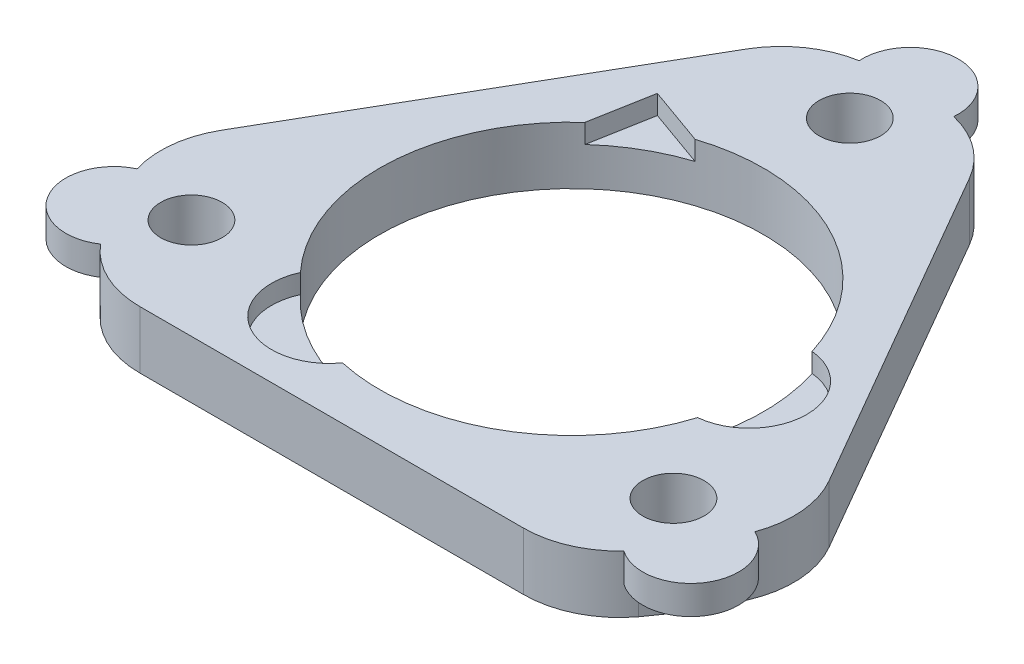
SolidWorks part; units mm, degrees
ref_plane "Спереди" through (0, 0, 0) normal (0, 0, 1) x (1, 0, 0)
ref_plane "Сверху" through (0, 0, 0) normal (0, 1, 0) x (1, 0, 0)
ref_plane "Справа" through (0, 0, 0) normal (1, 0, 0) x (0, 0, -1)
sketch "Sketch1" plane through (0, 0, 0) normal (0, 1, 0) x (1, 0, 0)
  circle A0 centre (0, 0) radius 18.5
  dimension "D1" = 37
extrude "Boss-Extrude1" add sketch "Sketch1" along normal blind 3.5
sketch "Sketch2" plane through (0, 0, 0) normal (0, 1, 0) x (1, 0, 0)
  circle A0 centre (0, 0) radius 35
  circle A1 centre (0, 0) radius 20
  circle A2 centre (0, 0) radius 29 construction
  circle A3 centre (0, 29) radius 2.8
  circle A4 centre (25.1147, -14.5) radius 2.8
  circle A5 centre (-25.1147, -14.5) radius 2.8
  point P16 (0, 0)
  dimension "D2" = 58
  dimension "D3" = 40
  dimension "D4" = 70
  dimension "D1" = 3
extrude "Boss-Extrude2" add sketch "Sketch2" along normal blind 6
sketch "Sketch4" plane through (0, 0, 0) normal (0, -1, 0) x (1, 0, 0)
  circle A0 centre (-25.1147, 14.5) radius 3.2
  circle A1 centre (25.1147, 14.5) radius 3.2
  circle A2 centre (0, -29) radius 3.2
  point P9 (0, 0)
  dimension "D1" = 3
sketch "Sketch5" plane through (0, 6, 0) normal (0, 1, 0) x (1, 0, 0)
  circle A0 centre (-30.4536, -17.2504) radius 5
  circle A1 centre (0, 0) radius 35 construction
  circle A2 centre (0.2875, 34.9988) radius 5
  circle A3 centre (30.1661, -17.7484) radius 5
  point P10 (0, 0)
  dimension "D1" = 3
extrude "Boss-Extrude4" add sketch "Sketch5" against normal blind 3
sketch "Sketch3" plane through (0, 3.5, 0) normal (0, 1, 0) x (1, 0, 0)
  circle A0 centre (0, 0) radius 18.5
  dimension "D1" = 37
extrude "Cut-Extrude1" cut sketch "Sketch3" against normal blind 10
sketch "Sketch12" plane through (0, 6, 0) normal (0, 1, 0) x (1, 0, 0)
  line L1 (0, 50) -> (-43.3013, -25)
  line L2 (-43.3013, -25) -> (43.3013, -25)
  line L3 (43.3013, -25) -> (0, 50)
  circle A0 centre (0, 0) radius 25 construction
  circle A1 centre (0, 0) radius 72.1359
extrude "Cut-Extrude2" cut sketch "Sketch12" against normal blind 22
fillet "Fillet1" radius 10 6 edges at (-24.4949, 3, 25) (-33.8981, 3, 8.7132) (24.4949, 3, 25) (33.8981, 3, 8.7132) (9.4032, 3, -33.7132) (-9.4032, 3, -33.7132)
sketch "Sketch15" plane through (0, 6, 0) normal (0, 1, 0) x (1, 0, 0)
  line L1 (-13.9004, 12.2078) -> (-3.6502, 18.1363)
  line L3 (-12.2665, 21.2081) -> (-13.9004, 12.2078)
  line L4 (-12.2665, 21.2081) -> (-3.6502, 18.1363)
  circle A1 centre (0, 0) radius 20 construction
  circle A2 centre (0, 0) radius 20
  circle A3 centre (18.5, 0.0144) radius 6
  circle A4 centre (-9.2376, -16.0287) radius 6
  circle A5 centre (0, 0) radius 20 construction
  point P15 (0, 0)
  circle M8 centre (0, 0) radius 20
extrude "Cut-Extrude4" cut sketch "Sketch15" against normal blind 2 contours A2 A4 | A2 A3 | L4 L3 M8 region at (-10.7165, 6, -18.5282) region at (-10.8343, 6, 18.7992) region at (21.6977, 6, -0.0169)
extrude "Cut-Extrude5" cut sketch "Sketch4" against normal blind 10
